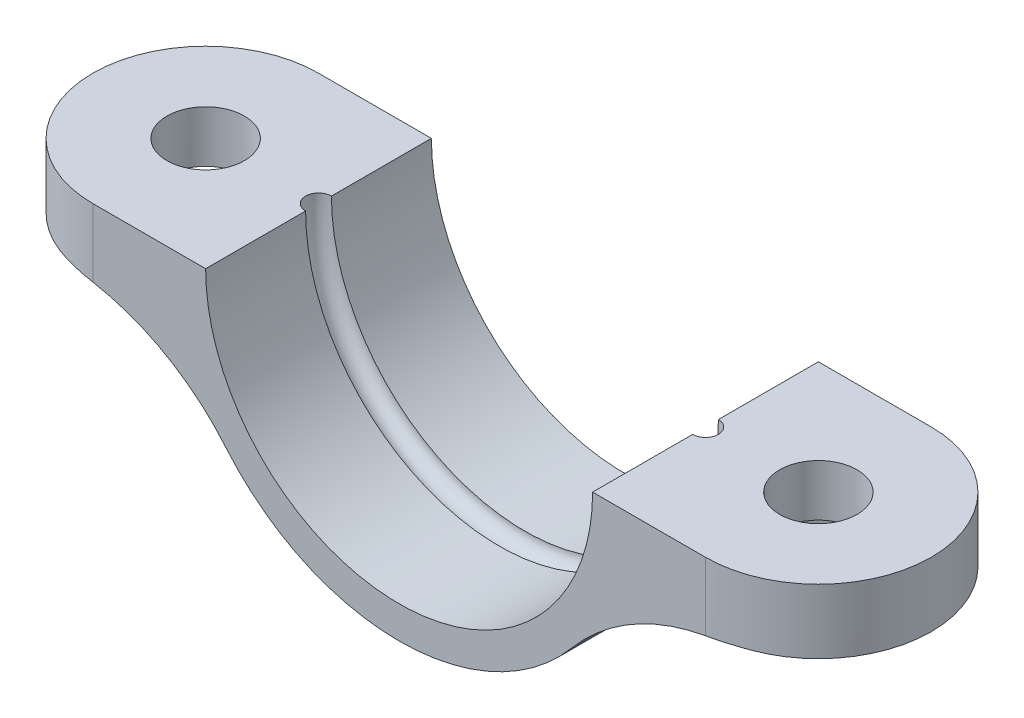
SolidWorks part; units mm, degrees
ref_plane "Front Plane" through (0, 0, 0) normal (0, 0, 1) x (1, 0, 0)
ref_plane "Top Plane" through (0, 0, 0) normal (0, 1, 0) x (1, 0, 0)
ref_plane "Right Plane" through (0, 0, 0) normal (1, 0, 0) x (0, 0, -1)
sketch "Sketch1" plane through (0, 0, 0) normal (0, 0, 1) x (1, 0, 0)
  line L0 (30, 0) -> (65, 0)
  line L1 (65, 0) -> (65, -10)
  line L2 (65, -10) -> (53.619, -10)
  line L3 (-65, 0) -> (-30, 0)
  line L4 (-65, 0) -> (-65, -10)
  line L5 (-65, -10) -> (-53.619, -10)
  arc A0 (-30, 0) -> (30, 0) centre (0, 0) ccw
  arc A1 (-26.8095, -22.5) -> (26.8095, -22.5) centre (0, 0) ccw
  arc A2 (-53.619, -10) -> (-26.8095, -22.5) centre (-53.619, -45) cw
  arc A3 (53.619, -10) -> (26.8095, -22.5) centre (53.619, -45) ccw
  dimension "D1" = 70
  dimension "D2" = 60
  dimension "D5" = 35
  dimension "D6" = 35
  dimension "D3" = 35
  dimension "D4" = 10
extrude "Boss-Extrude1" add sketch "Sketch1" along normal mid plane 35
sketch "Sketch2" plane through (0, 0, 0) normal (0, 1, 0) x (1, 0, 0)
  line L0 (30, 17.5) -> (65, -17.5) construction
  line L1 (0, 0) -> (0, 38.4242) construction
  circle A0 centre (47.5, 0) radius 6
  circle A1 centre (-47.5, 0) radius 6
  dimension "D1" = 12
extrude "Cut-Extrude1" cut sketch "Sketch2" against normal blind 35
sketch "Sketch3" plane through (0, 0, 0) normal (0, 1, 0) x (1, 0, 0)
  circle A0 centre (-47.5, 0) radius 10
  circle A1 centre (47.5, 0) radius 10
  dimension "D1" = 20
extrude "Cut-Extrude2" cut sketch "Sketch3" against normal blind 35 from offset 8 offset against normal yes
sketch "Sketch4" plane through (0, 0, 0) normal (0, 1, 0) x (1, 0, 0)
  line L0 (30, -17.5) -> (30, 17.5) construction
  line L1 (0, 0) -> (0, 33.9339) construction
  circle A0 centre (30, 0) radius 2
  dimension "D1" = 4
revolve "Cut-Revolve1" cut sketch "Sketch4" angle 360 about L1
fillet "Fillet1" 2 edges at (-65, -5, 17.5) (-65, -5, -17.5) type full round first side face at (0, -12.1557, 17.5) second side face at (0, -12.1557, -17.5) middle face at (-65, -5, 0)
fillet "Fillet2" 2 edges at (65, -5, 17.5) (65, -5, -17.5) type full round first side face at (9.8096, -12.583, 17.5) second side face at (9.8096, -12.583, -17.5) middle face at (65, -5, 0)
